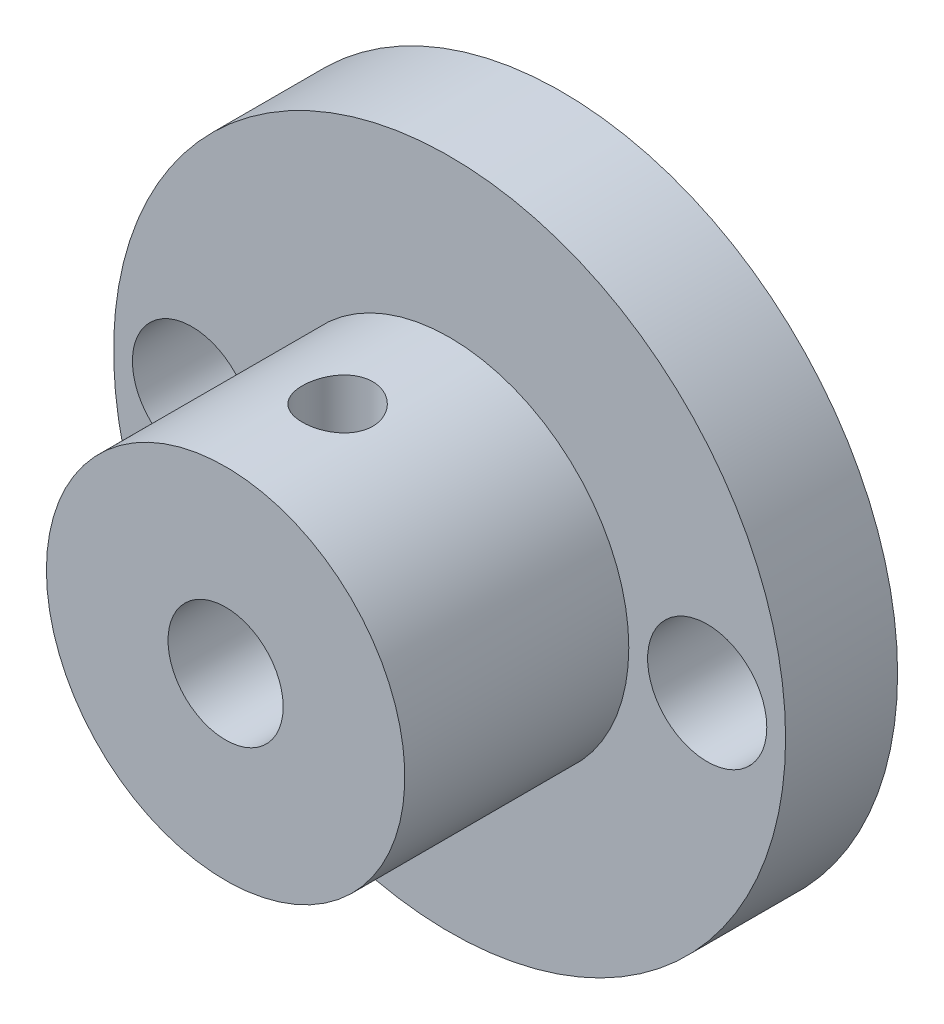
SolidWorks part; units mm, degrees
material "1060 Alloy"
ref_plane "Front" through (0, 0, 0) normal (0, 0, 1) x (1, 0, 0)
ref_plane "Top" through (0, 0, 0) normal (0, 1, 0) x (1, 0, 0)
ref_plane "Right" through (0, 0, 0) normal (1, 0, 0) x (0, 0, -1)
sketch "Sketch1" plane through (0, 0, 0) normal (0, 0, 1) x (1, 0, 0)
  circle A0 centre (0, 0) radius 19.05
  dimension "D1" = 38.1
extrude "Boss-Extrude1" add sketch "Sketch1" along normal blind 6.35
sketch "Sketch2" plane through (0, 0, 0) normal (0, 0, -1) x (-1, 0, 0)
  circle A0 centre (0, 0) radius 10.16
  dimension "D1" = 20.32
extrude "Boss-Extrude2" add sketch "Sketch2" against normal blind 19.05
hole_wizard "F (0.257) Diameter Hole1" positions "Sketch3" profile "Sketch4" hole size "F" standard "ANSI Inch" end condition through all
sketch "Sketch3" plane through (0, 0, 19.05) normal (0, 0, 1) x (1, 0, 0)
  point P0 (0, 0)
sketch "Sketch4" plane through (0, 0, 19.05) normal (1, 0, 0) x (0, -1, 0)
  line L0 (0, 0) -> (0, 19.05)
  line L1 (0, 19.05) -> (3.2639, 19.05)
  line L2 (3.2639, 19.05) -> (3.2639, 0)
  line L5 (3.2639, 0) -> (0, 0)
  line L11 (0, -6.35) -> (0, 107.95) construction
  dimension "Thru Hole Dia." = 6.5278
  dimension "Thru Hole Depth" = 19.05
hole_wizard "#10-24 Tapped Hole3" positions "3DSketch2" profile "Sketch9" tap size "#10-24" standard "ANSI Inch"
sketch3d "3DSketch2"
  point P0 (0, 10.16, 12.7)
  dimension "D1" = 12.7
cosmetic thread "Hole Thread7" parameters "D1"=3.7659, "D2"=4.826
sketch "Sketch9" plane through (0, 10.16, 12.7) normal (1, 0, 0) x (0, 0, 1)
  line L0 (0, 0) -> (0, 11.3571)
  line L1 (0, 11.3571) -> (1.9939, 10.159)
  line L2 (1.9939, 10.159) -> (1.9939, 0)
  line L5 (1.9939, 0) -> (0, 0)
  line L10 (0, 11.3571) -> (-1.9939, 10.159) construction
  line L11 (0, -6.35) -> (0, 107.95) construction
  dimension "Tap Drill Dia." = 3.9878
  dimension "Tap Drill Depth" = 10.159
  dimension "Drill Angle" = 118
sketch "Sketch11" plane through (0, 0, 6.35) normal (0, 0, 1) x (1, 0, 0)
  circle A0 centre (0, 0) radius 14.605 construction
  dimension "D1" = 29.21
hole_wizard "H (0.266) Diameter Hole1" positions "Sketch12" profile "Sketch13" hole size "H" standard "ANSI Inch" end condition through all
sketch "Sketch12" plane through (0, 0, 6.35) normal (0, 0, 1) x (1, 0, 0)
  circle A0 centre (0, 0) radius 14.605 construction
  point P0 (-14.605, 0)
  point P4 (14.605, 0)
sketch "Sketch13" plane through (-14.605, 0, 6.35) normal (1, 0, 0) x (0, -1, 0)
  line L0 (0, 0) -> (0, 6.35)
  line L1 (0, 6.35) -> (3.3782, 6.35)
  line L2 (3.3782, 6.35) -> (3.3782, 0)
  line L5 (3.3782, 0) -> (0, 0)
  line L11 (0, -6.35) -> (0, 107.95) construction
  dimension "Thru Hole Dia." = 6.7564
  dimension "Thru Hole Depth" = 6.35
